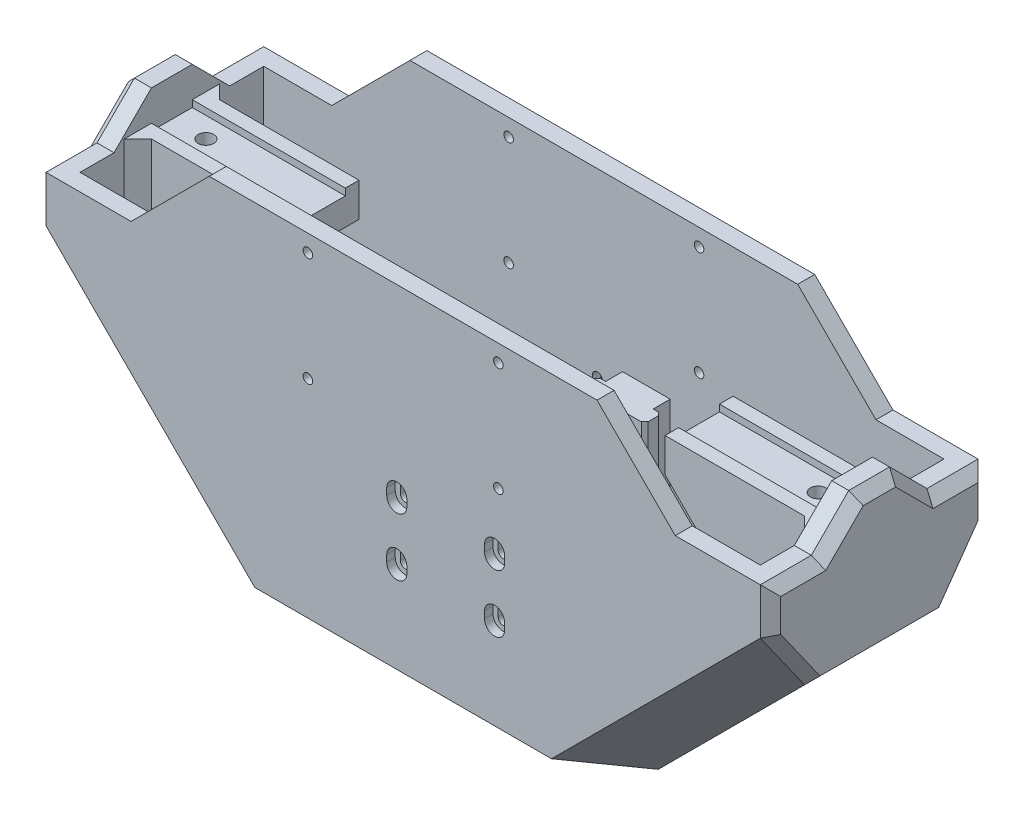
SolidWorks part; units mm, degrees
ref_plane "Front Plane" through (0, 0, 0) normal (0, 0, 1) x (1, 0, 0)
ref_plane "Top Plane" through (0, 0, 0) normal (0, 1, 0) x (1, 0, 0)
ref_plane "Right Plane" through (0, 0, 0) normal (1, 0, 0) x (0, 0, -1)
sketch "Sketch1" plane through (0, 0, 0) normal (0, 1, 0) x (1, 0, 0)
  line L1 (-100, -27) -> (100, -27)
  line L2 (-100, -27) -> (-100, 27)
  line L3 (-100, 27) -> (100, 27)
  line L4 (100, -27) -> (100, 27)
  line L5 (-100, -27) -> (100, 27) construction
  line L6 (-100, 27) -> (100, -27) construction
  point P0 (0, 0)
  dimension "D1" = 200
  dimension "D2" = 54
extrude "Boss-Extrude1" add sketch "Sketch1" along normal blind 70
shell "Shell1" thickness 5 removed face at (0, 70, 0) outward yes
sketch "Sketch2" plane through (105, 0, 0) normal (1, 0, 0) x (0, 0, -1)
  line L0 (-17, 70) -> (-6, 81)
  line L1 (-32, 70) -> (32, 70) construction
  line L2 (-6, 81) -> (6, 81)
  line L3 (6, 81) -> (17, 70)
  line L4 (17, 70) -> (-17, 70)
  line L5 (0, 81) -> (0, 75) construction
  dimension "D1" = 11
  dimension "D2" = 45
  dimension "D3" = 45
  dimension "D4" = 12
extrude "Boss-Extrude2" add sketch "Sketch2" against normal blind 5
sketch "Sketch4" plane through (0, 0, -32) normal (0, 0, -1) x (-1, 0, 0)
  line L0 (-80, 70) -> (-57, 93)
  line L1 (-105, 70) -> (105, 70) construction
  line L2 (-57, 93) -> (57, 93)
  line L3 (57, 93) -> (80, 70)
  line L4 (80, 70) -> (-80, 70)
  line L5 (0, 93) -> (0, 70) construction
  line L6 (-105, 70) -> (-105, -5) construction
  dimension "D1" = 23
  dimension "D2" = 25
  dimension "D3" = 45
extrude "Boss-Extrude3" add sketch "Sketch4" against normal blind 5
sketch "Sketch3" plane through (0, 0, -32) normal (0, 0, -1) x (-1, 0, 0)
  line L1 (-28, 56) -> (28, 56) construction
  line L2 (-28, 56) -> (-28, 88) construction
  line L3 (-28, 88) -> (28, 88) construction
  line L4 (28, 56) -> (28, 88) construction
  line L5 (-28, 56) -> (28, 88) construction
  line L6 (-28, 88) -> (28, 56) construction
  line L7 (57, 93) -> (-57, 93) construction
  circle A0 centre (-28, 88) radius 1.4
  circle A1 centre (-28, 56) radius 1.4
  circle A2 centre (28, 88) radius 1.4
  circle A3 centre (28, 56) radius 1.4
  point P0 (0, 72)
  dimension "D1" = 2.8
  dimension "D2" = 56
  dimension "D3" = 32
  dimension "D4" = 5
extrude "Cut-Extrude1" cut sketch "Sketch3" against normal blind 6
mirror "Mirror4" about plane through (0, 0, 0) normal (0, 0, 1) of "Boss-Extrude3", "Cut-Extrude1"
mirror "Mirror5" about plane through (0, 0, 0) normal (1, 0, 0) of "Boss-Extrude2"
sketch "Sketch5" plane through (0, 0, 0) normal (0, 0, 1) x (1, 0, 0)
  line L0 (-100, 70) -> (-55, 70)
  line L1 (-55, 70) -> (-55, 62)
  line L2 (-55, 62) -> (-100, 17)
  line L4 (-100, 17) -> (-100, 70)
  line L5 (-100, 81) -> (-100, 70) construction
  line L6 (-105, 70) -> (-80, 70) construction
  dimension "D1" = 45
  dimension "D2" = 8
  dimension "D3" = 45
extrude "Boss-Extrude4" add sketch "Sketch5" along normal mid plane 20
sketch "Sketch9" plane through (0, 70, 0) normal (0, 1, 0) x (1, 0, 0)
  line L4 (-55, 10) -> (-100, 10)
  line L5 (-100, 10) -> (-100, -10)
  line L6 (-100, -10) -> (-55, -10)
  line L7 (-55, -10) -> (-55, 10)
  line L8 (-55, 10) -> (-100, 10)
  line L10 (-100, -10) -> (-55, -10)
  line L11 (-55, -10) -> (-55, 10)
  line L13 (-100, 10) -> (-100, -10)
  dimension "D1" = 0
extrude "Boss-Extrude6" add sketch "Sketch9" along normal blind 2
sketch "Sketch10" plane through (-100, 0, 0) normal (1, 0, 0) x (0, 0, -1)
  line L0 (-10, 72) -> (10, 72) construction
  line L1 (-6, 72) -> (6, 72)
  line L2 (-6, 72) -> (-6, 70)
  line L3 (-6, 70) -> (6, 70)
  line L4 (6, 72) -> (6, 70)
  line L5 (-6, 72) -> (6, 70) construction
  line L6 (-6, 70) -> (6, 72) construction
  point P0 (0, 71)
  dimension "D1" = 2
  dimension "D2" = 12
extrude "Cut-Extrude2" cut sketch "Sketch10" along normal up to next
sketch "Sketch11" plane through (0, 70, 0) normal (0, 1, 0) x (1, 0, 0)
  line L1 (-100, 6) -> (-100, -6) construction
  circle A0 centre (-90, 0) radius 2.3
  dimension "D1" = 4.6
  dimension "D2" = 10
extrude "Cut-Extrude3" cut sketch "Sketch11" against normal blind 6
mirror "Mirror24" about plane through (0, 0, 0) normal (1, 0, 0) of "Cut-Extrude2", "Boss-Extrude4", "Boss-Extrude6", "Cut-Extrude3"
chamfer "Chamfer3" distance 40 angle 45 2 edges at (100, 0, 0) (-100, 0, 0)
chamfer "Chamfer5" distance 43 angle 45 2 edges at (105, -5, 0) (-105, -5, 0)
chamfer "Chamfer11" distance 10 angle 45 4 edges at (80, 20, 27) (80, 20, -27) (-80, 20, -27) (-80, 20, 27)
chamfer "Chamfer12" distance 13 angle 45 4 edges at (83.5, 16.5, -32) (83.5, 16.5, 32) (-83.5, 16.5, -32) (-83.5, 16.5, 32)
chamfer "Chamfer13" distance 4 angle 45 4 edges at (-100, 56, 10) (-100, 56, -10) (100, 56, 10) (100, 56, -10)
sketch "Sketch16" plane through (105, 0, 0) normal (1, 0, 0) x (0, 0, -1)
  line L10 (-19, 38) -> (19, 38)
  line L11 (19, 38) -> (32, 56.3848)
  line L12 (32, 56.3848) -> (32, 70)
  line L13 (32, 70) -> (17, 70)
  line L14 (17, 70) -> (6, 81)
  line L15 (6, 81) -> (-6, 81)
  line L16 (-6, 81) -> (-17, 70)
  line L17 (-17, 70) -> (-32, 70)
  line L18 (-32, 70) -> (-32, 56.3848)
  line L19 (-32, 56.3848) -> (-19, 38)
  line L20 (-19, 38) -> (19, 38)
  line L21 (19, 38) -> (32, 56.3848)
  line L22 (32, 56.3848) -> (32, 70)
  line L23 (32, 70) -> (17, 70)
  line L24 (17, 70) -> (6, 81)
  line L25 (6, 81) -> (-6, 81)
  line L26 (-6, 81) -> (-17, 70)
  line L27 (-17, 70) -> (-32, 70)
  line L28 (-32, 70) -> (-32, 56.3848)
  line L29 (-32, 56.3848) -> (-19, 38)
  dimension "D1" = 0
extrude "Boss-Extrude10" add sketch "Sketch16" along normal blind 3
chamfer "Chamfer14" distance 3 angle 45 10 edges at (108, 63.1924, 32) (108, 70, 24.5) (108, 75.5, 11.5) (108, 81, 0) (108, 75.5, -11.5) (108, 70, -24.5) (108, 63.1924, -32) (108, 47.1924, -25.5) (108, 38, 0) (108, 47.1924, 25.5)
mirror "Mirror28" about plane through (0, 0, 0) normal (1, 0, 0) of "Chamfer14", "Boss-Extrude10"
sketch "Sketch17" plane through (0, 0, 0) normal (0, 1, 0) x (1, 0, 0)
  line L0 (-57, -27) -> (57, -27) construction
  line L1 (5.5, -27) -> (19.5, -27)
  line L2 (5.5, -27) -> (5.5, -22)
  line L3 (5.5, -22) -> (19.5, -22)
  line L4 (19.5, -27) -> (19.5, -22)
  line L5 (5.5, -27) -> (19.5, -22) construction
  line L6 (5.5, -22) -> (19.5, -27) construction
  line L7 (3, -22) -> (22, -22)
  line L8 (3, -22) -> (3, -17)
  line L9 (3, -17) -> (22, -17)
  line L10 (22, -22) -> (22, -17)
  line L11 (3, -22) -> (22, -17) construction
  line L12 (3, -17) -> (22, -22) construction
  point P0 (12.5, -24.5)
  point P5 (12.5, -19.5)
  line M10 (-45.8579, -27) -> (45.8579, -27)
  dimension "D1" = 19
  dimension "D2" = 14
  dimension "D3" = 5
  dimension "D4" = 12.5
extrude "Boss-Extrude11" add sketch "Sketch17" along normal blind 45 contours L7 L10 L9 L8 L3 | L4 L3 L2 M10 region at (12.5, 0, 24.5) region at (12.5, 0, 19.5)
sketch "Sketch20" plane through (0, 0, 0) normal (0, 1, 0) x (1, 0, 0)
  line L0 (22, -22) -> (22, -17) construction
  line L1 (3, -17) -> (22, -17)
  line L2 (3, -17) -> (3, -12)
  line L3 (3, -12) -> (22, -12)
  line L4 (22, -17) -> (22, -12)
  dimension "D1" = 5
extrude "Boss-Extrude14" add sketch "Sketch20" along normal blind 8
mirror "Mirror29" about plane through (0, 0, 0) normal (0, 0, 1) of "Boss-Extrude14", "Boss-Extrude11"
sketch "Sketch22" plane through (0, 0, -27) normal (0, 0, 1) x (1, 0, 0)
  line L0 (5.5, 0) -> (-45.8579, 0) construction
  line L1 (-1.875, 21.8) -> (26.875, 21.8) construction
  line L2 (-1.875, 21.8) -> (-1.875, 38.8) construction
  line L3 (-1.875, 38.8) -> (26.875, 38.8) construction
  line L4 (26.875, 21.8) -> (26.875, 38.8) construction
  line L5 (-1.875, 21.8) -> (26.875, 38.8) construction
  line L6 (-1.875, 38.8) -> (26.875, 21.8) construction
  line L7 (3, 45) -> (22, 45) construction
  line L8 (-1.875, 37.8) -> (-1.875, 39.8) construction
  line L9 (-3.325, 37.8) -> (-3.325, 39.8)
  line L10 (-0.425, 37.8) -> (-0.425, 39.8)
  line L11 (12.5, 38.8) -> (12.5, 30.3) construction
  line L12 (12.5, 30.3) -> (-1.875, 30.3) construction
  line L13 (26.875, 37.8) -> (26.875, 39.8) construction
  line L14 (28.325, 37.8) -> (28.325, 39.8)
  line L15 (25.425, 37.8) -> (25.425, 39.8)
  line L16 (-1.875, 22.8) -> (-1.875, 20.8) construction
  line L17 (-3.325, 22.8) -> (-3.325, 20.8)
  line L18 (-0.425, 22.8) -> (-0.425, 20.8)
  line L19 (26.875, 22.8) -> (26.875, 20.8) construction
  line L20 (28.325, 22.8) -> (28.325, 20.8)
  line L21 (25.425, 22.8) -> (25.425, 20.8)
  arc A4 (-3.325, 37.8) -> (-0.425, 37.8) centre (-1.875, 37.8) ccw
  arc A5 (-0.425, 39.8) -> (-3.325, 39.8) centre (-1.875, 39.8) ccw
  arc A6 (28.325, 37.8) -> (25.425, 37.8) centre (26.875, 37.8) cw
  arc A7 (25.425, 39.8) -> (28.325, 39.8) centre (26.875, 39.8) cw
  arc A8 (-3.325, 22.8) -> (-0.425, 22.8) centre (-1.875, 22.8) cw
  arc A9 (-0.425, 20.8) -> (-3.325, 20.8) centre (-1.875, 20.8) cw
  arc A10 (28.325, 22.8) -> (25.425, 22.8) centre (26.875, 22.8) ccw
  arc A11 (25.425, 20.8) -> (28.325, 20.8) centre (26.875, 20.8) ccw
  point P0 (12.5, 30.3)
  point P7 (12.5, 45)
  point P11 (-1.875, 38.8)
  point P22 (26.875, 38.8)
  point P29 (-1.875, 21.8)
  point P36 (26.875, 21.8)
  dimension "D4" = 1.45
  dimension "D1" = 21.8
  dimension "D2" = 28.75
  dimension "D3" = 17
  dimension "D5" = 2
extrude "Cut-Extrude4" cut sketch "Sketch22" against normal blind 2.5
sketch "Sketch23" plane through (0, 0, -29.5) normal (0, 0, 1) x (1, 0, 0)
  line L6 (29.825, 37.8) -> (29.825, 39.8)
  line L7 (23.925, 39.8) -> (23.925, 37.8)
  line L8 (29.825, 37.8) -> (29.825, 39.8)
  line L9 (23.925, 39.8) -> (23.925, 37.8)
  line L12 (1.075, 37.8) -> (1.075, 39.8)
  line L13 (-4.825, 39.8) -> (-4.825, 37.8)
  line L14 (1.075, 37.8) -> (1.075, 39.8)
  line L15 (-4.825, 39.8) -> (-4.825, 37.8)
  line L18 (-4.825, 22.8) -> (-4.825, 20.8)
  line L19 (1.075, 20.8) -> (1.075, 22.8)
  line L20 (-4.825, 22.8) -> (-4.825, 20.8)
  line L21 (1.075, 20.8) -> (1.075, 22.8)
  line L24 (23.925, 22.8) -> (23.925, 20.8)
  line L25 (29.825, 20.8) -> (29.825, 22.8)
  line L26 (23.925, 22.8) -> (23.925, 20.8)
  line L27 (29.825, 20.8) -> (29.825, 22.8)
  arc A6 (23.925, 37.8) -> (29.825, 37.8) centre (26.875, 37.8) ccw
  arc A7 (29.825, 39.8) -> (23.925, 39.8) centre (26.875, 39.8) ccw
  arc A8 (23.925, 37.8) -> (29.825, 37.8) centre (26.875, 37.8) ccw
  arc A9 (29.825, 39.8) -> (23.925, 39.8) centre (26.875, 39.8) ccw
  arc A12 (-4.825, 37.8) -> (1.075, 37.8) centre (-1.875, 37.8) ccw
  arc A13 (1.075, 39.8) -> (-4.825, 39.8) centre (-1.875, 39.8) ccw
  arc A14 (-4.825, 37.8) -> (1.075, 37.8) centre (-1.875, 37.8) ccw
  arc A15 (1.075, 39.8) -> (-4.825, 39.8) centre (-1.875, 39.8) ccw
  arc A18 (1.075, 22.8) -> (-4.825, 22.8) centre (-1.875, 22.8) ccw
  arc A19 (-4.825, 20.8) -> (1.075, 20.8) centre (-1.875, 20.8) ccw
  arc A20 (1.075, 22.8) -> (-4.825, 22.8) centre (-1.875, 22.8) ccw
  arc A21 (-4.825, 20.8) -> (1.075, 20.8) centre (-1.875, 20.8) ccw
  arc A24 (29.825, 22.8) -> (23.925, 22.8) centre (26.875, 22.8) ccw
  arc A25 (23.925, 20.8) -> (29.825, 20.8) centre (26.875, 20.8) ccw
  arc A26 (29.825, 22.8) -> (23.925, 22.8) centre (26.875, 22.8) ccw
  arc A27 (23.925, 20.8) -> (29.825, 20.8) centre (26.875, 20.8) ccw
  dimension "D1" = 1.5
  dimension "D2" = 1.5
  dimension "D3" = 1.5
  dimension "D4" = 1.5
extrude "Cut-Extrude5" cut sketch "Sketch23" against normal up to next contours A8 L8 A9 L9 | A14 L14 A15 L15 | A20 L20 A21 L21 | A26 L26 A27 L27
mirror "Mirror30" about plane through (0, 0, 0) normal (0, 0, 1) of "Cut-Extrude5", "Cut-Extrude4"
sketch "Sketch24" plane through (30, -30, 0) normal (-0.7071, 0.7071, 0) x (0, 0, 1)
  line L0 (17, 42.4264) -> (-17, 42.4264) construction
  line L1 (-7.5, 47.4264) -> (7.5, 47.4264)
  line L2 (-7.5, 47.4264) -> (-7.5, 55.4264)
  line L3 (-7.5, 55.4264) -> (7.5, 55.4264)
  line L4 (7.5, 47.4264) -> (7.5, 55.4264)
  line L5 (-7.5, 47.4264) -> (7.5, 55.4264) construction
  line L6 (-7.5, 55.4264) -> (7.5, 47.4264) construction
  point P0 (0, 51.4264)
  dimension "D1" = 5
  dimension "D2" = 15
  dimension "D3" = 8
extrude "Cut-Extrude6" cut sketch "Sketch24" against normal up to next
chamfer "Chamfer18" distance 4 angle 45 4 edges at (22, 0, 17) (22, 0, -17) (3, 0, 17) (3, 0, -17)
chamfer "Chamfer19" distance 1 angle 45 8 edges at (3, 24.5, 22) (22, 26.5, 17) (22, 24.5, 22) (3, 26.5, 17) (22, 24.5, -22) (22, 26.5, -17) (3, 26.5, -17) (3, 24.5, -22)
chamfer "Chamfer20" distance 2 angle 45 4 edges at (65.2855, 1.7855, -7.5) (65.2855, 1.7855, 7.5) (70.9424, 7.4424, 7.5) (70.9424, 7.4424, -7.5)
